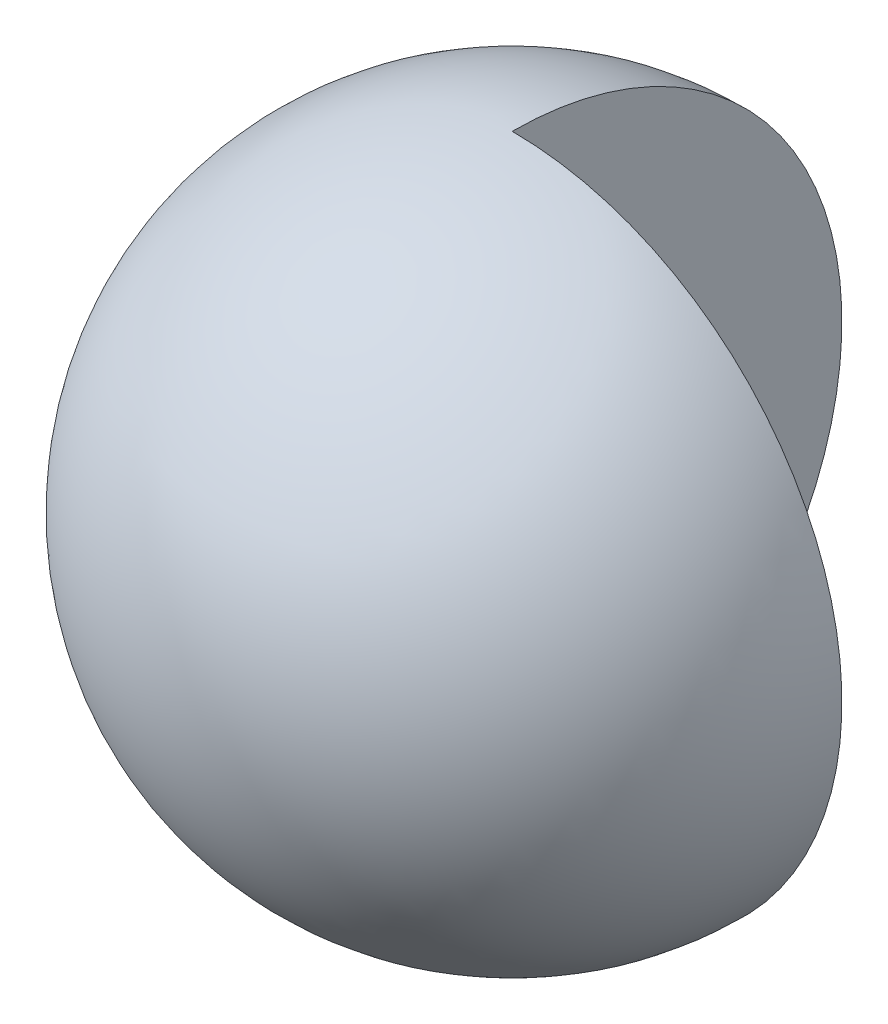
SolidWorks part; units mm, degrees
ref_plane "Front Plane" through (0, 0, 0) normal (0, 0, 1) x (1, 0, 0)
ref_plane "Top Plane" through (0, 0, 0) normal (0, 1, 0) x (1, 0, 0)
ref_plane "Right Plane" through (0, 0, 0) normal (1, 0, 0) x (0, 0, -1)
sketch "Sketch2" plane through (0, 0, 0) normal (0, 0, 1) x (1, 0, 0)
  line L0 (0, 5) -> (0, -5)
  arc A0 (0, -5) -> (0, 5) centre (0, 0) ccw
  dimension "D1" = 10
sketch "Sketch3" plane through (0, 0, 0) normal (0, 0, 1) x (1, 0, 0)
  line L0 (0, 5) -> (0, -5)
  circle A0 centre (0, 0) radius 5 construction
  point P5 (0, 0)
  point P6 (0, 0)
  point P7 (0, 0)
  point P8 (0, -5)
revolve "Revolve2" add sketch "Sketch2" angle 360 about L0
extrude "Cut-Extrude3" cut sketch "Sketch2<2>" against normal blind 21
sketch "Sketch2<2>" plane through (0, 0, 0) normal (0, 0, 1) x (1, 0, 0) same geometry as "Sketch2"
